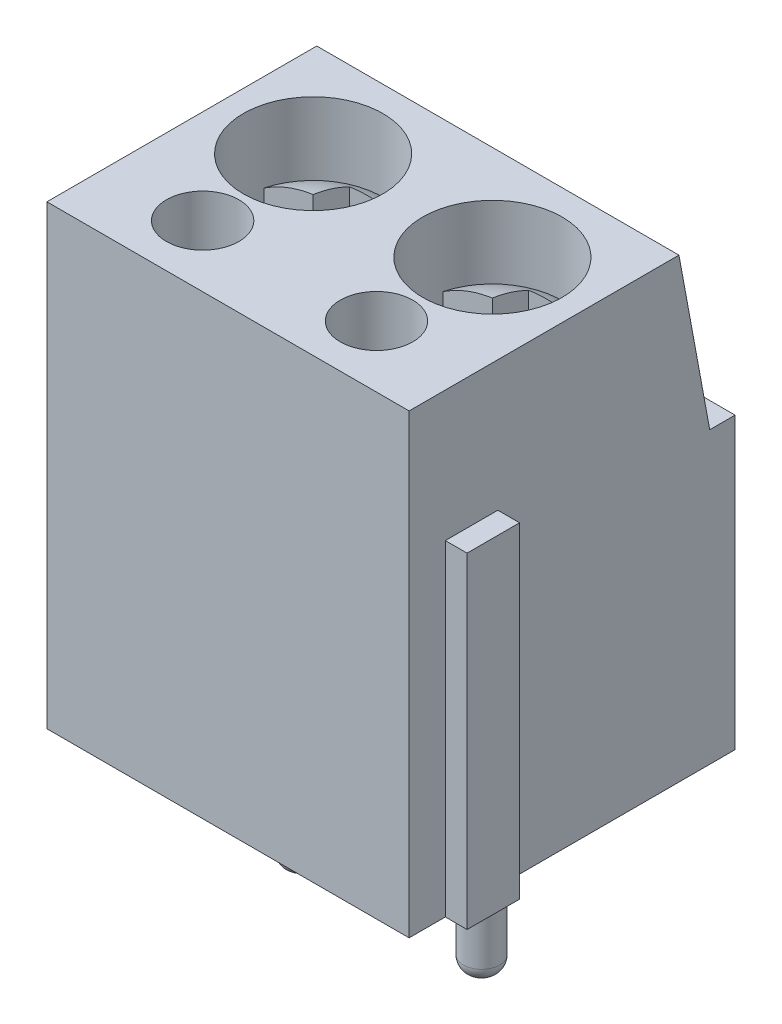
SolidWorks part; units mm, degrees
ref_plane "Plano frontal" through (0, 0, 0) normal (0, 0, 1) x (1, 0, 0)
ref_plane "Plano superior" through (0, 0, 0) normal (0, 1, 0) x (1, 0, 0)
ref_plane "Plano direito" through (0, 0, 0) normal (1, 0, 0) x (0, 0, -1)
sketch "Sketch1" plane through (0, 0, 0) normal (1, 0, 0) x (0, 0, -1)
  line L0 (0, 0) -> (0, 12.6)
  line L1 (0, 12.6) -> (7.45, 12.6)
  line L2 (7.45, 12.6) -> (8.3, 8)
  line L3 (8.3, 8) -> (9, 8)
  line L4 (9, 8) -> (9, 0)
  line L5 (9, 0) -> (0, 0)
  dimension "D1" = 12.6
  dimension "D2" = 7.45
  dimension "D3" = 9
  dimension "D4" = 8
  dimension "D5" = 0.7
extrude "Boss-Extrude1" add sketch "Sketch1" along normal blind 10
sketch "Sketch2" plane through (0, 0, -9) normal (0, 0, -1) x (-1, 0, 0)
  line L0 (0, 0) -> (0, 8) construction
  line L1 (-9.5, 7) -> (-5.5, 7)
  line L2 (-9.5, 7) -> (-9.5, 1)
  line L3 (-9.5, 1) -> (-5.5, 1)
  line L4 (-5.5, 7) -> (-5.5, 1)
  line L5 (-4.5, 7) -> (-0.5, 7)
  line L6 (-4.5, 7) -> (-4.5, 1)
  line L7 (-4.5, 1) -> (-0.5, 1)
  line L8 (-0.5, 7) -> (-0.5, 1)
  line L9 (-10, 0) -> (-10, 8) construction
  line L10 (-10, 0) -> (0, 0) construction
  line L11 (-10, 8) -> (0, 8) construction
  dimension "D1" = 0.5
  dimension "D2" = 1
  dimension "D3" = 0.5
  dimension "D4" = 1
  dimension "D5" = 1
extrude "Cut-Extrude1" cut sketch "Sketch2" against normal blind 2
sketch "Sketch3" plane through (0, 0, -9) normal (0, 0, -1) x (-1, 0, 0)
  line L0 (-9.5, 1) -> (-5.5, 1) construction
  line L1 (-8, 1) -> (-7, 1)
  line L2 (-8, 1) -> (-8, 0)
  line L3 (-8, 0) -> (-7, 0)
  line L4 (-7, 1) -> (-7, 0)
  line L5 (-10, 0) -> (0, 0) construction
  line L6 (-4.5, 1) -> (-0.5, 1) construction
  line L7 (-3, 1) -> (-2, 1)
  line L8 (-3, 1) -> (-3, 0)
  line L9 (-3, 0) -> (-2, 0)
  line L10 (-2, 1) -> (-2, 0)
  line L11 (0, 0) -> (0, 8) construction
  line L12 (-10, 0) -> (-10, 8) construction
  dimension "D1" = 2
  dimension "D2" = 2
  dimension "D3" = 4
extrude "Cut-Extrude2" cut sketch "Sketch3" against normal blind 5
sketch "Sketch4" plane through (0, 0, -7) normal (0, 0, -1) x (-1, 0, 0)
  line L1 (-3, 1) -> (-2, 1) construction
  line L2 (-5.5, 7) -> (-9.5, 7) construction
  line L3 (-0.5, 7) -> (-4.5, 7) construction
  circle A0 centre (-7.5, 3.5) radius 1.5
  circle A1 centre (-2.5, 3.5) radius 1.5
  point P8 (-7.5, 7)
  point P11 (-2.5, 7)
  dimension "D1" = 3
  dimension "D2" = 1
extrude "Cut-Extrude3" cut sketch "Sketch4" against normal blind 5
sketch "Sketch6" plane through (0, 0, -7) normal (0, 0, -1) x (-1, 0, 0)
  line L0 (-9.5, 7) -> (-8.5, 4)
  line L1 (-8.5, 4) -> (-6.5, 4)
  line L2 (-6.5, 4) -> (-5.5, 7)
  line L3 (-5.5, 7) -> (-9.5, 7)
  line L4 (-5.5, 7) -> (-4.5, 7) construction
  line L5 (-5, 7) -> (-5, 0.9151) construction
  line L6 (-4.5, 7) -> (-0.5, 7)
  line L7 (-3.5, 4) -> (-4.5, 7)
  line L8 (-1.5, 4) -> (-3.5, 4)
  line L9 (-0.5, 7) -> (-1.5, 4)
  dimension "D1" = 3
  dimension "D2" = 2
extrude "Boss-Extrude2" add sketch "Sketch6" along normal blind 0.1
sketch "Sketch7" plane through (0, 1, 0) normal (0, -1, 0) x (1, 0, 0)
  line L6 (2, -4) -> (2, -9) construction
  line L8 (3, -4) -> (3, -9) construction
  line L10 (2, -4) -> (3, -4) construction
  line L13 (8, -4) -> (7, -4) construction
  line L16 (8, -4) -> (8, -9) construction
  line L18 (7, -4) -> (7, -7) construction
  circle A0 centre (2.5, -4.5) radius 0.499
  circle A1 centre (7.5, -4.5) radius 0.499
  dimension "D1" = 0.001
  dimension "D2" = 0.001
  dimension "D3" = 0.001
  dimension "D4" = 0.001
  dimension "D5" = 0.001
  dimension "D6" = 0.001
extrude "Boss-Extrude5" add sketch "Sketch7" along normal blind 5.3
sketch "Sketch8" plane through (0, 0, 0) normal (-1, 0, 0) x (0, 0, 1)
  line L0 (0, 0) -> (-9, 0) construction
  line L1 (-2.3, 0) -> (-1, 0)
  line L2 (-2.3, 0) -> (-2.3, 9)
  line L3 (-2.3, 9) -> (-1, 9)
  line L4 (-1, 0) -> (-1, 9)
  line L5 (0, 12.6) -> (0, 0) construction
  dimension "D1" = 1.3
  dimension "D2" = 9
  dimension "D3" = 1
extrude "Cut-Extrude4" cut sketch "Sketch8" against normal blind 0.6
sketch "Sketch9" plane through (10, 0, 0) normal (1, 0, 0) x (0, 0, -1)
  line L0 (0, 0) -> (9, 0) construction
  line L1 (1, 0) -> (2.45, 0)
  line L2 (1, 0) -> (1, 9)
  line L3 (1, 9) -> (2.45, 9)
  line L4 (2.45, 0) -> (2.45, 9)
  line L5 (0, 12.6) -> (0, 0) construction
  dimension "D1" = 1
  dimension "D2" = 1.45
  dimension "D3" = 9
extrude "Boss-Extrude6" add sketch "Sketch9" along normal blind 0.6
sketch "Sketch10" plane through (0, 12.6, 0) normal (0, 1, 0) x (1, 0, 0)
  line L3 (0, 7.45) -> (0, 0) construction
  line L6 (10, 0) -> (0, 0) construction
  line L8 (10, 7.45) -> (0, 7.45) construction
  line L9 (5, 7.45) -> (5, 0) construction
  circle A0 centre (2.525, 4.825) radius 1.925
  circle A1 centre (7.4, 1.7) radius 1
  circle A2 centre (2.6, 1.7) radius 1
  circle A3 centre (7.475, 4.825) radius 1.925
  dimension "D1" = 3.85
  dimension "D2" = 2
  dimension "D4" = 0.6
  dimension "D5" = 1.6
  dimension "D7" = 0.7
  dimension "D8" = 0.7
extrude "Cut-Extrude5" cut sketch "Sketch10" against normal blind 2
sketch "Sketch11" plane through (0, 0, -7.1) normal (0, 0, -1) x (-1, 0, 0)
  line L0 (-4.5, 7) -> (-5.5, 7) construction
  line L1 (-8.5, 4) -> (-6.5, 4)
  line L2 (-8.5, 4) -> (-8.5, 3.9)
  line L3 (-8.5, 3.9) -> (-6.5, 3.9)
  line L4 (-6.5, 4) -> (-6.5, 3.9)
  line L5 (-5, 7) -> (-5, 2.7412) construction
  line L6 (-3.5, 4) -> (-3.5, 3.9)
  line L7 (-1.5, 3.9) -> (-3.5, 3.9)
  line L8 (-1.5, 4) -> (-1.5, 3.9)
  line L9 (-1.5, 4) -> (-3.5, 4)
  dimension "D1" = 0.1
extrude "Boss-Extrude7" add sketch "Sketch11" against normal blind 3
fillet "Fillet1" radius 0.1 2 edges at (2.5, 3.9, -7.1) (7.5, 3.9, -7.1)
fillet "Fillet2" radius 0.4 2 edges at (7.5, -4.3, -4.999) (2.5, -4.3, -4.999)
sketch "Sketch12" plane through (0, 10.6, 0) normal (0, 1, 0) x (1, 0, 0)
  line L0 (5.55, 4.825) -> (9.4, 4.825)
  circle A0 centre (7.475, 4.825) radius 1.925 construction
  circle A1 centre (7.475, 4.825) radius 1.925 construction
ref_plane "Plane1" through (0, 0, -4.825) normal (0, 0, 1) x (1, 0, 0)
sketch "Sketch13" plane through (0, 0, -4.825) normal (0, 0, 1) x (1, 0, 0)
  line L0 (7.475, 10.6) -> (7.475, 11.5349) construction
  line L1 (5.55, 10.6) -> (9.4, 10.6) construction
  line L2 (7.475, 11.1979) -> (7.475, 10.6)
  line L3 (7.475, 10.6) -> (9.4, 10.6)
  arc A0 (7.475, 11.1979) -> (9.4, 10.6) centre (7.475, 7.8) cw
revolve "Revolve1" add sketch "Sketch13" angle 360 about L0
ref_plane "Plane2" through (5, 0, 0) normal (1, 0, 0) x (0, 0, -1)
sketch "Sketch15" plane through (0, 12.6, 0) normal (0, 1, 0) x (1, 0, 0)
  line L0 (7.475, 6.75) -> (7.475, 2.9) construction
  line L1 (6.975, 6.325) -> (7.975, 6.325)
  line L2 (6.975, 6.325) -> (6.975, 3.325)
  line L3 (6.975, 3.325) -> (7.975, 3.325)
  line L4 (7.975, 6.325) -> (7.975, 3.325)
  line L5 (5.6161, 5.325) -> (9.3339, 5.325)
  line L7 (5.6161, 4.325) -> (9.3339, 4.325)
  line L10 (9.4, 4.825) -> (5.55, 4.825) construction
  arc A0 (5.6161, 5.325) -> (5.6161, 4.325) centre (7.475, 4.825) ccw
  circle A1 centre (7.475, 4.825) radius 1.925 construction
  circle A2 centre (7.475, 4.825) radius 1.925 construction
  arc A3 (9.3339, 4.325) -> (9.3339, 5.325) centre (7.475, 4.825) ccw
  point P4 (7.975, 4.825)
  point P5 (7.475, 6.325)
  circle M1 centre (7.475, 4.825) radius 1.925
  dimension "D1" = 1
  dimension "D2" = 1
  dimension "D3" = 3
  dimension "D4" = 0.5
extrude "Cut-Extrude6" cut sketch "Sketch15" against normal blind 3 contours L4 L7 L5 M1 | L2 L7 L4 L5 | L2 L5 L4 L1 | L7 L2 L5 M1 | L7 L2 L3 L4 region at (7.475, 12.6, -5.825) region at (7.475, 12.6, -4.825) region at (6.2733, 12.6, -4.825) region at (8.6767, 12.6, -4.825) region at (7.475, 12.6, -3.825)
mirror "Mirror1" about plane through (5, 0, 0) normal (1, 0, 0) of "Cut-Extrude6", "Revolve1"
sketch "Sketch16" plane through (0, 10.6, 0) normal (0, 1, 0) x (1, 0, 0)
  circle A1 centre (2.6, 1.7) radius 1
  circle A2 centre (2.6, 1.7) radius 1
  circle A3 centre (7.4, 1.7) radius 1
  circle A4 centre (7.4, 1.7) radius 1
  dimension "D1" = 0
  dimension "D2" = 0
extrude "Cut-Extrude7" cut sketch "Sketch16" against normal blind 3
sketch "Sketch17" plane through (0, 9.6, 0) normal (0, 1, 0) x (1, 0, 0)
  line L10 (2.025, 5.325) -> (0.6661, 5.325)
  line L11 (0.6661, 4.325) -> (2.025, 4.325)
  line L12 (2.025, 4.325) -> (2.025, 3.325)
  line L13 (2.025, 3.325) -> (3.025, 3.325)
  line L14 (3.025, 3.325) -> (3.025, 4.325)
  line L15 (3.025, 4.325) -> (4.3839, 4.325)
  line L16 (4.3839, 5.325) -> (3.025, 5.325)
  line L17 (3.025, 5.325) -> (3.025, 6.325)
  line L18 (3.025, 6.325) -> (2.025, 6.325)
  line L19 (2.025, 6.325) -> (2.025, 5.325)
  line L20 (2.025, 5.325) -> (0.6661, 5.325)
  line L21 (0.6661, 4.325) -> (2.025, 4.325)
  line L22 (2.025, 4.325) -> (2.025, 3.325)
  line L23 (2.025, 3.325) -> (3.025, 3.325)
  line L24 (3.025, 3.325) -> (3.025, 4.325)
  line L25 (3.025, 4.325) -> (4.3839, 4.325)
  line L26 (4.3839, 5.325) -> (3.025, 5.325)
  line L27 (3.025, 5.325) -> (3.025, 6.325)
  line L28 (3.025, 6.325) -> (2.025, 6.325)
  line L29 (2.025, 6.325) -> (2.025, 5.325)
  line L30 (9.3339, 5.325) -> (7.975, 5.325)
  line L31 (7.975, 5.325) -> (7.975, 6.325)
  line L32 (7.975, 6.325) -> (6.975, 6.325)
  line L33 (6.975, 6.325) -> (6.975, 5.325)
  line L34 (6.975, 5.325) -> (5.6161, 5.325)
  line L35 (5.6161, 4.325) -> (6.975, 4.325)
  line L36 (6.975, 4.325) -> (6.975, 3.325)
  line L37 (6.975, 3.325) -> (7.975, 3.325)
  line L38 (7.975, 3.325) -> (7.975, 4.325)
  line L39 (7.975, 4.325) -> (9.3339, 4.325)
  line L40 (9.3339, 5.325) -> (7.975, 5.325)
  line L41 (7.975, 5.325) -> (7.975, 6.325)
  line L42 (7.975, 6.325) -> (6.975, 6.325)
  line L43 (6.975, 6.325) -> (6.975, 5.325)
  line L44 (6.975, 5.325) -> (5.6161, 5.325)
  line L45 (5.6161, 4.325) -> (6.975, 4.325)
  line L46 (6.975, 4.325) -> (6.975, 3.325)
  line L47 (6.975, 3.325) -> (7.975, 3.325)
  line L48 (7.975, 3.325) -> (7.975, 4.325)
  line L49 (7.975, 4.325) -> (9.3339, 4.325)
  arc A2 (0.6661, 5.325) -> (0.6661, 4.325) centre (2.525, 4.825) ccw
  arc A3 (4.3839, 4.325) -> (4.3839, 5.325) centre (2.525, 4.825) ccw
  arc A4 (0.6661, 5.325) -> (0.6661, 4.325) centre (2.525, 4.825) ccw
  arc A5 (4.3839, 4.325) -> (4.3839, 5.325) centre (2.525, 4.825) ccw
  arc A6 (5.6161, 5.325) -> (5.6161, 4.325) centre (7.475, 4.825) ccw
  arc A7 (9.3339, 4.325) -> (9.3339, 5.325) centre (7.475, 4.825) ccw
  arc A8 (5.6161, 5.325) -> (5.6161, 4.325) centre (7.475, 4.825) ccw
  arc A9 (9.3339, 4.325) -> (9.3339, 5.325) centre (7.475, 4.825) ccw
  dimension "D1" = 0
  dimension "D2" = 0
extrude "Cut-Extrude8" cut sketch "Sketch17" against normal blind 1 draft 20
